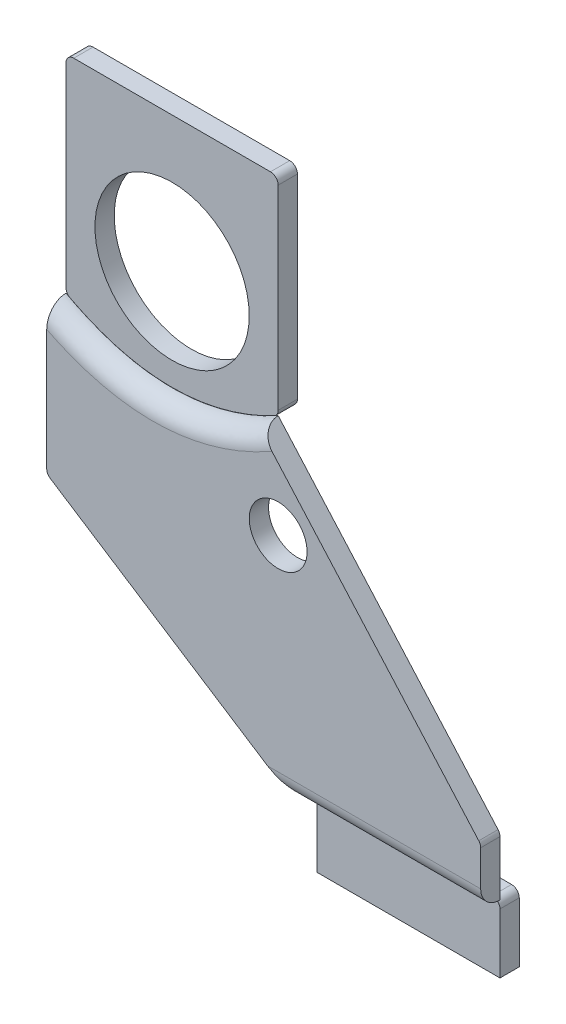
SolidWorks part; units mm, degrees
ref_plane "Front Plane" through (0, 0, 0) normal (0, 0, 1) x (1, 0, 0)
ref_plane "Top Plane" through (0, 0, 0) normal (0, 1, 0) x (1, 0, 0)
ref_plane "Right Plane" through (0, 0, 0) normal (1, 0, 0) x (0, 0, -1)
sketch "Sketch1" plane through (0, 0, 0) normal (0, 0, 1) x (1, 0, 0)
  line L0 (-0.5, 30) -> (-0.5, -30) construction
  line L1 (-22.5, 30) -> (22.5, 30) construction
  line L2 (-22.5, 30) -> (-22.5, -30) construction
  line L3 (-22.5, -30) -> (22.5, -30) construction
  line L4 (22.5, 30) -> (22.5, -30) construction
  line L5 (-22.5, 5) -> (22.5, 5) construction
  line L6 (-22.5, -18) -> (22.5, -18) construction
  line L7 (-22.5, -5) -> (22.5, -5) construction
  line L8 (-22.5, 8) -> (22.5, 8) construction
  line L9 (3.5, -30) -> (3.5, 30) construction
  line L10 (-22.5, -28) -> (22.5, -28) construction
  line L11 (-22.5, -24) -> (22.5, -24) construction
  line L12 (22.5, -18) -> (22.5, -24)
  line L13 (22.5, -18) -> (-0.5, 8)
  line L14 (-22.5, 8) -> (-22.5, -7.22)
  line L15 (22.5, -24) -> (3.5, -24)
  line L16 (3.5, -24) -> (-22.5, -7.22)
  spline S0 degree 2 poles (-0.5, 8) (-11.5, 2) (-22.5, 8) knots 0 0 0 1 1 1
  point P0 (0, 0)
  point P8 (-11.5, 5)
  dimension "D1" = 45
  dimension "D2" = 60
  dimension "D3" = 15.22
  dimension "D4" = 6
  dimension "D6" = 19
  dimension "D7" = 2
  dimension "D9" = 11
  dimension "D10" = 35
extrude "Boss-Extrude1" add sketch "Sketch1" along normal blind 2
ref_plane "Plane1" through (0, 0, -2) normal (0, 0, 1) x (1, 0, 0)
sketch "Sketch25" plane through (0, 0, -2) normal (0, 0, 1) x (1, 0, 0)
  line L0 (3.5, -24) -> (3.5, -31)
  line L1 (3.5, -31) -> (22.5, -31)
  line L2 (22.5, -31) -> (22.5, -24)
  line L3 (22.5, -24) -> (3.5, -24)
  line L4 (-22.5, 8) -> (-22.5, 29.5)
  line L5 (-22.5, 29.5) -> (-0.5, 29.5)
  line L6 (-0.5, 29.5) -> (-0.5, 8)
  line L7 (-11.5, 29.5) -> (-11.5, 5.0271) construction
  spline S0 degree 2 poles (-22.5, 8) (-11.5, 2.0543) (-0.5, 8) knots 0 0 0 1 1 1
  point P14 (-11.5, 15.46)
  dimension "D1" = 7
  dimension "D2" = 21.5
  dimension "D3" = 14.04
extrude "Boss-Extrude14" add sketch "Sketch25" along normal blind 2 separate body
sketch "Sketch26" plane through (0, 0, 0) normal (0, 0, 1) x (1, 0, 0)
  line L0 (-22.5, 26) -> (-0.5, 26) construction
  line L1 (-22.5, 29.5) -> (-22.5, 8) construction
  line L2 (-0.5, 8) -> (-0.5, 29.5) construction
  line L3 (-11.5, 26) -> (-11.5, 4.9267) construction
  line L4 (-0.5, 29.5) -> (-22.5, 29.5) construction
  circle A0 centre (-11.5, 15.4634) radius 8
  dimension "D2" = 16
  dimension "D1" = 18
  dimension "D3" = 14.0366
extrude "Cut-Extrude4" cut sketch "Sketch26" against normal through all
sketch "Sketch27" plane through (0, 0, 2) normal (0, 0, 1) x (1, 0, 0)
  line L0 (-22.5, -7.22) -> (15.6779, -7.22) construction
  line L1 (-0.5, 8) -> (-0.5, -7.22) construction
  line L2 (1.5, -7.22) -> (1.5, 5.7391) construction
  line L3 (22.5, -18) -> (-0.5, 8) construction
  circle A0 centre (1.5, -0.7404) radius 3
  dimension "D2" = 6
  dimension "D1" = 2
extrude "Cut-Extrude5" cut sketch "Sketch27" against normal through all
fillet "Fillet6" radius 2 2 edges at (13, -24, 2)
fillet "Fillet7" radius 0.8 4 edges at (-0.5, 8, -1) (-22.5, 8, -1) (-0.5, 29.5, -1) (-22.5, 29.5, -1)
fillet "Fillet8" radius 0.8 2 edges at (22.5, -18, 1) (-22.5, -7.22, 1)
fillet "Fillet9" radius 0.8 2 edges at (3.5, -24, -1) (22.5, -24, -1)
